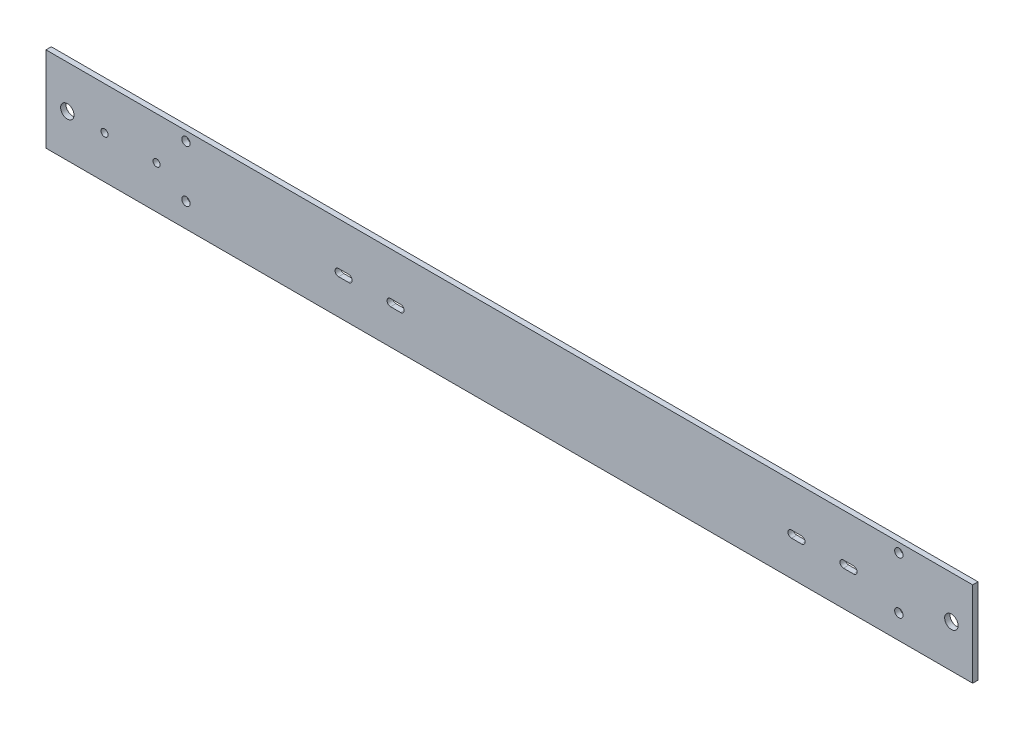
SolidWorks part; units mm, degrees
ref_plane "Front Plane" through (0, 0, 0) normal (0, 0, 1) x (1, 0, 0)
ref_plane "Top Plane" through (0, 0, 0) normal (0, 1, 0) x (1, 0, 0)
ref_plane "Right Plane" through (0, 0, 0) normal (1, 0, 0) x (0, 0, -1)
sketch "Sketch1" plane through (0, 0, 0) normal (1, 0, 0) x (0, 0, -1)
  line L0 (0, 0) -> (-3.175, 0)
  line L3 (-3.175, 0) -> (-3.175, 50.8)
  line L4 (-3.175, 50.8) -> (0, 50.8)
  line L5 (0, 50.8) -> (0, 0)
  dimension "LHeight" = 50.8
  dimension "LMaterialThickness" = 3.175
extrude "Boss-Extrude1" add sketch "Sketch1" along normal blind 552.45
sketch "SideHoles-Sketch4" plane through (0, 0, 3.175) normal (0, 0, 1) x (1, 0, 0)
  line L1 (444.425, 23) -> (450.425, 23) construction
  line L2 (444.425, 25.1) -> (450.425, 25.1)
  line L3 (444.425, 20.9) -> (450.425, 20.9)
  line L4 (552.45, 0) -> (0, 0) construction
  line L5 (475.425, 23) -> (481.425, 23) construction
  line L6 (0, 50.8) -> (0, 0) construction
  line L7 (552.45, 50.8) -> (552.45, 0) construction
  line L8 (475.425, 25.1) -> (481.425, 25.1)
  line L9 (475.425, 20.9) -> (481.425, 20.9)
  line L10 (174.425, 23) -> (180.425, 23) construction
  line L11 (174.425, 25.1) -> (180.425, 25.1)
  line L12 (174.425, 20.9) -> (180.425, 20.9)
  line L13 (205.425, 23) -> (211.425, 23) construction
  line L14 (205.425, 25.1) -> (211.425, 25.1)
  line L15 (205.425, 20.9) -> (211.425, 20.9)
  line L16 (552.45, 50.8) -> (0, 50.8) construction
  line L22 (552.45, 0) -> (552.45, 50.8) construction
  line L23 (552.45, 50.8) -> (0, 50.8) construction
  circle A6 centre (12.7, 25.4) radius 4
  circle A9 centre (539.75, 25.4) radius 4
  arc A37 (444.425, 25.1) -> (444.425, 20.9) centre (444.425, 23) ccw
  arc A38 (450.425, 20.9) -> (450.425, 25.1) centre (450.425, 23) ccw
  arc A39 (475.425, 25.1) -> (475.425, 20.9) centre (475.425, 23) ccw
  arc A40 (481.425, 20.9) -> (481.425, 25.1) centre (481.425, 23) ccw
  arc A41 (174.425, 25.1) -> (174.425, 20.9) centre (174.425, 23) ccw
  arc A42 (180.425, 20.9) -> (180.425, 25.1) centre (180.425, 23) ccw
  arc A43 (205.425, 25.1) -> (205.425, 20.9) centre (205.425, 23) ccw
  arc A44 (211.425, 20.9) -> (211.425, 25.1) centre (211.425, 23) ccw
  circle A45 centre (83.425, 45.3) radius 2.5
  circle A46 centre (83.425, 14.3) radius 2.5
  circle A47 centre (508.425, 45.3) radius 2.5
  circle A48 centre (508.425, 14.3) radius 2.5
  circle A53 centre (34.9, 25.4) radius 2.1
  circle A54 centre (65.9, 25.4) radius 2.1
  point P2 (447.425, 23)
  point P9 (478.425, 23)
  point P19 (177.425, 23)
  point P66 (208.425, 23)
  dimension "D3" = 8
  dimension "D6" = 4.2
  dimension "D8" = 5
  dimension "D7" = 25.4
  dimension "D2" = 12.7
  dimension "D4" = 12.7
  dimension "D5" = 6
  dimension "D13" = 31
  dimension "D16" = 31
  dimension "D19" = 270
  dimension "D15" = 74.025
  dimension "D9" = 31
  dimension "D10" = 5.5
  dimension "D11" = 44.025
  dimension "D12" = 425
  dimension "D21" = 177.425
  dimension "D23" = 469.025
  dimension "D24" = 344.025
  dimension "D25" = 375.025
  dimension "D14" = 27.8
  dimension "D27" = 539.75
  dimension "D17" = 34.9
  dimension "D18" = 31
  dimension "D20" = 486.55
  dimension "D22" = 517.55
  dimension "D26" = 105.025
extrude "SideHoles-Cut-Extrude3" cut sketch "SideHoles-Sketch4" against normal through all
equation "\"MidLeftOrRightSideRailHeight\"= 2.0in"
equation "\"RailThickness\"= .125in'Spec"
equation "\"VSWidth\"= 1.25in'Spec"
equation "\"LHeight@Sketch1\"=\"MidLeftOrRightSideRailHeight\""
equation "\"LMaterialThickness@Sketch1\"=\"RailThickness\""
equation "\"D1@Boss-Extrude1\" = \"SideRailLength\""
equation "\"SideRailLength\"= 21.75in"
equation "\"D7@SideHoles-Sketch4\"=\"MidLeftOrRightSideRailHeight\"/2"
equation "\"DistanceFromFrontSideToBedFrontYSValue\"= 48.525mm"
equation "\"DistanceBetweenFrontToBackStepperHoles\"= \"BedLength\" - \"BuildPlateStandoffHolesDistanceFromFrontOrBackSide\" * 2'Equals 270"
equation "\"DistanceFromFrontSideToFirstLeftStepperHoleMountYSValue\"= 74.025mm"
equation "\"FrameFastenerHoleOffsetFromEdge\"= \"VSWidth\" / 2 - \"GapBetweenVerticalSupportsAndRails\" / 2"
equation "\"D2@SideHoles-Sketch4\"=\"FrameFastenerHoleOffsetFromEdge\""
equation "\"FrameFastenerHoleDiameter\"= 8mm"
equation "\"D3@SideHoles-Sketch4\"=\"FrameFastenerHoleDiameter\""
equation "\"D4@SideHoles-Sketch4\"=\"FrameFastenerHoleOffsetFromEdge\""
equation "\"StepperMountSlotDiameterOnRails\"= 4.2mm"
equation "\"StepperMountSlotWidth\"= 6mm"
equation "\"D5@SideHoles-Sketch4\"=\"StepperMountSlotWidth\""
equation "\"D6@SideHoles-Sketch4\"=\"StepperMountSlotDiameterOnRails\""
equation "\"D13@SideHoles-Sketch4\" = \"Nema17StepperMountSlotDistance\""
equation "\"D16@SideHoles-Sketch4\" = \"Nema17StepperMountSlotDistance\""
equation "\"D19@SideHoles-Sketch4\"=\"DistanceBetweenFrontToBackStepperHoles\""
equation "\"D15@SideHoles-Sketch4\"=\"DistanceFromFrontSideToFirstLeftStepperHoleMountYSValue\""
equation "\"D10@SideHoles-Sketch4\"=\"SK8MountHoleFromEitherEnd\""
equation "\"RodShaft440mmLength\"= 440mm"
equation "\"SK8RodShaftSupportLength\"= 15mm"
equation "\"D11@SideHoles-Sketch4\"=\"DistanceFromFrontSideToBedFrontYSValue\" - (\"SK8RodShaftSupportLength\" /2) + 3mm"
equation "\"D12@SideHoles-Sketch4\"=\"RodShaft440mmLength\"-\"SK8RodShaftSupportLength\""
equation "\"BuildPlateStandoffHolesDistanceFromFrontOrBackSide\"= 41mm"
equation "\"SK8MountHoleFromEitherEnd\"= 5.5mm"
equation "\"BuildPlateLength\"= 352mm'Spec"
equation "\"BedLength\"= \"BuildPlateLength\""
equation "\"Nema17StepperMountSlotDistance\"= 31mm'Spec"
equation "\"GapBetweenVerticalSupportsAndRails\"= \"RailThickness\" * 2"
equation "\"D14@SideHoles-Sketch4\"=27.8"
equation "\"D18@SideHoles-Sketch4\"=\"Nema17StepperMountSlotDistance\""
equation "\"DistanceFromBackToFirstGantryStepperHole\"= \"VSWidth\" - \"RailThickness\" + ( \"Nema17MountWidth\" - \"Nema17StepperMountSlotDistance\" ) / 2 - \"GapBetweenVerticalSupportsAndRails\" / 2'Equals 34.9. Push Gantry stepper as far back as possible"
equation "\"D17@SideHoles-Sketch4\"=\"DistanceFromBackToFirstGantryStepperHole\""
equation "\"Nema17MountWidth\"= 50mm'Spec"
